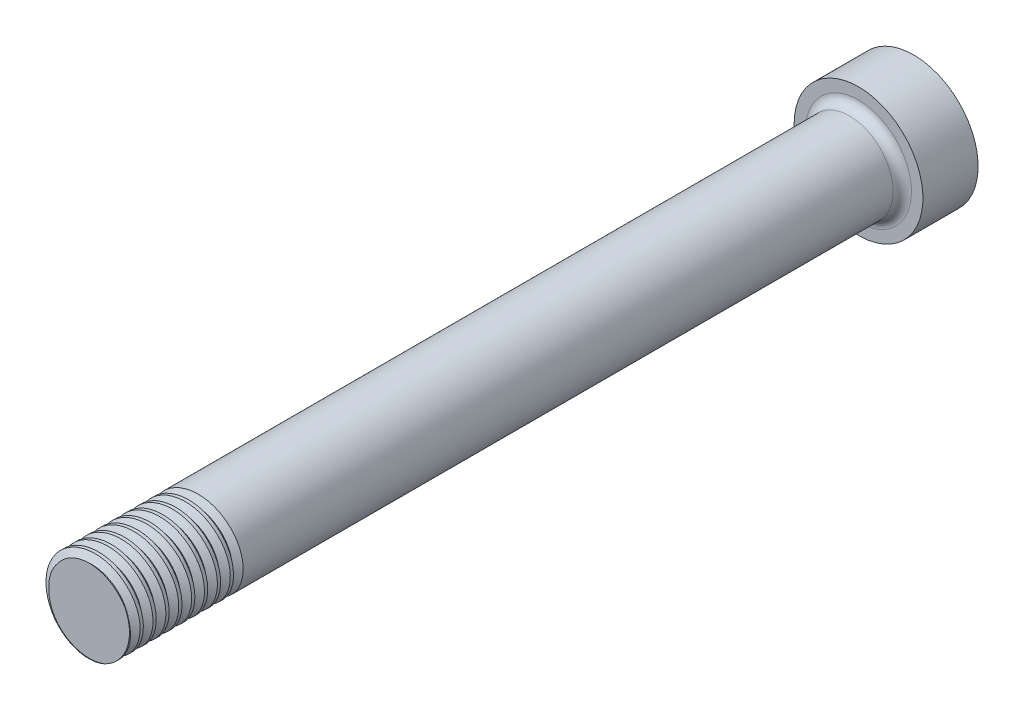
SolidWorks part; units mm, degrees
ref_plane "Alzado" through (0, 0, 0) normal (0, 0, 1) x (1, 0, 0)
ref_plane "Planta" through (0, 0, 0) normal (0, 1, 0) x (1, 0, 0)
ref_plane "Vista lateral" through (0, 0, 0) normal (1, 0, 0) x (0, 0, -1)
sketch "Croquis1" plane through (0, 0, 0) normal (0, 0, 1) x (1, 0, 0)
  circle A0 centre (0, 0) radius 2.3813
  dimension "D1" = 4.7625
extrude "Saliente-Extruir1" add sketch "Croquis1" along normal blind 73
sketch "Croquis2" plane through (0, 0, 0) normal (0, 0, -1) x (-1, 0, 0)
  circle A0 centre (0, 0) radius 4
  dimension "D1" = 8
extrude "Saliente-Extruir4" add sketch "Croquis2" against normal blind 3 draft 28.5
thread "Rosca1" pitch 0.3175 method cut profile "Perfil de rosca1" start angle 0, offset 2, length 8, pitch 0.3175, diameter 4.7625
ref_plane "Plano1" through (-2.3813, 0, 75) normal (0, -1, 0) x (-1, 0, 0)
sketch "Perfil de rosca1" plane through (-2.3813, 0, 75) normal (0, -1, 0) x (-1, 0, 0)
  line L0 (0, 0) -> (0, 0.3175) construction
  line L11 (0, 0) -> (0, 0.2778)
  line L12 (0, 0.2778) -> (-0.1719, 0.1786)
  line L13 (-0.1719, 0.1786) -> (-0.1719, 0.0992)
  line L15 (-0.1719, 0.0992) -> (0, 0)
  line L17 (-0.1719, 0.1389) -> (0, 0.1389) construction
  point P2 (0, 0)
  dimension "Pitch" = 0.3175
  dimension "Profile_Angle" = 60
  dimension "Profile_Land" = 0.0794
  dimension "Profile_Height" = 0.1719
sketch "Croquis10" plane through (0, 0, 0) normal (0, 0, -1) x (-1, 0, 0)
  line L0 (0, 1.5875) -> (1.3748, 0.7938) construction
  line L1 (1.3748, 0.7938) -> (1.3748, -0.7938) construction
  line L2 (1.3748, -0.7938) -> (0, -1.5875) construction
  line L4 (-1.3748, -0.7938) -> (0, -1.5875) construction
  line L5 (-1.3748, 0.7938) -> (-1.3748, -0.7938) construction
  line L6 (0, 1.5875) -> (-1.3748, 0.7938) construction
  line L7 (0, -1.5875) -> (0, -1.9844) construction
  line L8 (1.3748, 0.7938) -> (1.7185, 0.9922) construction
  line L9 (-1.3748, -0.7938) -> (-1.7185, -0.9922) construction
  line L10 (1.3748, -0.7938) -> (1.7185, -0.9922) construction
  line L11 (0, 1.5875) -> (0, 1.9844) construction
  line L14 (-1.3748, 0.7938) -> (-1.7185, 0.9922) construction
  circle A2 centre (0, 0) radius 1.9844
  circle A3 centre (0, 0) radius 1.5875 construction
  spline S0 degree 3 poles (0.4759, 0.8243) (2.2209, 1.2822) (0.9518, 0) (2.2209, -1.2822) (0.4759, -0.8243) (0, -2.5644) (-0.4759, -0.8243) (-2.2209, -1.2822) (-0.9518, 0) (-2.2209, 1.2822) (-0.4759, 0.8243) (0, 2.5644) (0.4759, 0.8243) (2.2209, 1.2822) (0.9518, 0) knots -0.25 -0.166667 -0.083333 0 0.083333 0.166667 0.25 0.333333 0.416667 0.5 0.583333 0.666667 0.75 0.833333 0.916667 1 1.083333 1.166667 1.25 only from (1.7185, 0.9922) to (1.7185, 0.9922)
  circle M1 centre (0, 0) radius 4
  dimension "D1" = 3.175
  dimension "D2" = 3.9688
  dimension "D3" = 120
extrude "Cortar-Extruir2" cut sketch "Croquis10" against normal blind 8 contours S0 M1 region at (0, 0, 0)
sketch "Croquis11" plane through (0, 0, 0) normal (0, 0, -1) x (-1, 0, 0)
  circle A0 centre (0, 0) radius 2.3813
  circle A1 centre (0, 0) radius 4.3252
  dimension "D1" = 4.7625
extrude "Cortar-Extruir3" cut sketch "Croquis11" against normal blind 8
sketch "Croquis22" plane through (0, 0, 0) normal (0, 0, -1) x (-1, 0, 0)
  circle A0 centre (0, 0) radius 3.5
  circle A1 centre (0, 0) radius 2.3813
  dimension "D1" = 7
extrude "Saliente-Extruir8" add sketch "Croquis22" against normal blind 3
fillet "Redondeo2" radius 0.5 1 edges at (-2.3813, 0, 3) type face fillet first side face at (-2.3813, 0, 3) second side face at (0.8909, 1.862, 71.4307)
sketch "Croquis23" plane through (0, 0, 73) normal (0, 0, 1) x (1, 0, 0)
  circle A0 centre (0, 0) radius 2.3812
extrude "Cortar-Extruir4" cut sketch "Croquis23" against normal blind 28
thread "Rosca3" pitch 0.7 method cut profile "Perfil de rosca4" start angle 0, offset 1, length 7, pitch 0.7, diameter 4.7625
ref_plane "Plano4" through (-2.3813, 0, 46) normal (0, 1, 0) x (1, 0, 0)
sketch "Perfil de rosca4" plane through (-2.3813, 0, 46) normal (0, 1, 0) x (1, 0, 0)
  line L0 (0, 0) -> (0, 0.7) construction
  line L1 (0, 0) -> (0.3789, 0.2187)
  line L2 (0.3789, 0.2187) -> (0.3789, 0.3062)
  line L3 (0.3789, 0.3062) -> (0, 0.525)
  line L4 (0.3789, 0.2625) -> (0, 0.2625) construction
  line L11 (0, 0) -> (0, 0.525)
  point P2 (0, 0)
  dimension "Pitch" = 0.7
  dimension "Profile_Angle" = 60
  dimension "Profile_Land" = 0.0875
  dimension "Profile_Height" = 0.3789
